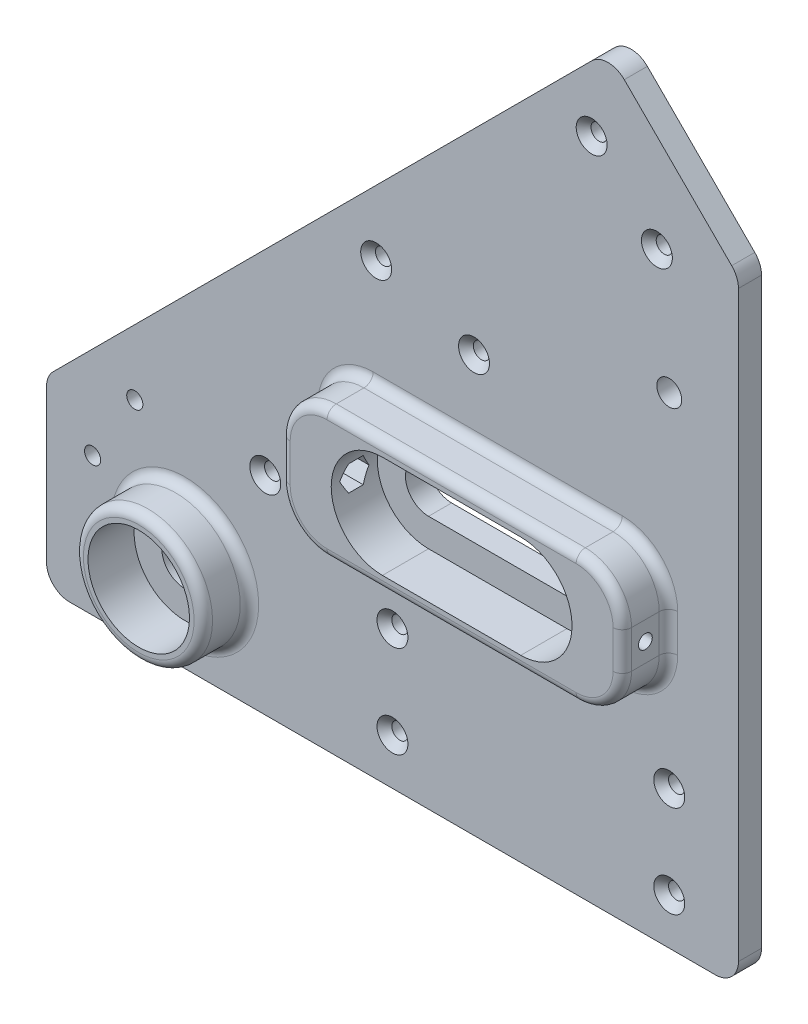
SolidWorks part; units mm, degrees
ref_plane "Front Plane" through (0, 0, 0) normal (0, 0, 1) x (1, 0, 0)
ref_plane "Top Plane" through (0, 0, 0) normal (0, 1, 0) x (1, 0, 0)
ref_plane "Right Plane" through (0, 0, 0) normal (1, 0, 0) x (0, 0, -1)
sketch "Sketch1" plane through (0, 0, 0) normal (0, 0, 1) x (1, 0, 0)
  line L0 (-75, 20) -> (46.7157, 141.7157)
  line L1 (-18.4315, 20) -> (75, 20) construction
  line L2 (-75, 20) -> (-75, -20)
  line L3 (-75, -20) -> (75, -20)
  line L4 (75, 20) -> (75, -20)
  line L5 (-75, 20) -> (75, -20) construction
  line L6 (-75, -20) -> (75, 20) construction
  line L7 (-75, -20) -> (75, -20)
  line L11 (46.7157, 141.7157) -> (75, 113.4315)
  line L12 (75, 113.4315) -> (-18.4315, 20) construction
  line L13 (-75, 0) -> (75, 0) construction
  line L14 (-75, 10) -> (75, 10) construction
  line L15 (-75, -10) -> (75, -10) construction
  line L16 (60.8579, 127.5736) -> (-46.7157, 20) construction
  line L17 (-75, 20) -> (-18.4315, 20) construction
  line L18 (53.7868, 134.6447) -> (-60.8579, 20) construction
  line L19 (67.9289, 120.5025) -> (-32.5736, 20) construction
  line L20 (75, 113.4315) -> (75, 20)
  line L21 (43.1802, 124.0381) -> (57.3223, 109.8959) construction
  line L22 (60, -10) -> (60, 10) construction
  line L23 (-65, -10) -> (-65, 10) construction
  line L24 (7.8202, 40) -> (37.8202, 40) construction
  line L25 (7.8202, 45) -> (37.8202, 45)
  line L26 (7.8202, 35) -> (37.8202, 35)
  line L27 (60, 10) -> (60, 98.4315) construction
  circle A0 centre (-45, 0) radius 5
  circle A1 centre (22.8202, 40) radius 5 construction
  circle A2 centre (-65, -10) radius 1.75
  circle A3 centre (0, 10) radius 1.75
  circle A4 centre (60, -10) radius 1.75
  circle A5 centre (-55.8579, 25) radius 1.75
  circle A6 centre (43.1802, 124.0381) radius 1.75
  circle A8 centre (-27.5736, 25) radius 1.75
  circle A9 centre (57.3223, 109.8959) radius 1.75
  circle A10 centre (22.8202, 40) radius 4 construction
  circle A11 centre (-3.5355, 77.3223) radius 1.75
  circle A12 centre (17.6777, 70.2513) radius 1.75
  circle A13 centre (60, 10) radius 1.75
  circle A14 centre (-65, 10) radius 1.75
  circle A15 centre (0, -10) radius 1.75
  arc A16 (7.8202, 45) -> (7.8202, 35) centre (7.8202, 40) ccw
  arc A17 (37.8202, 35) -> (37.8202, 45) centre (37.8202, 40) ccw
  circle A18 centre (60, 84.2893) radius 2.7
  point P0 (0, 0)
  point P50 (22.8202, 40)
  dimension "D8" = 10
  dimension "D11" = 10
  dimension "D12" = 3.5
  dimension "D17" = 30
  dimension "D18" = 5.4
  dimension "D1" = 40
  dimension "D2" = 40
  dimension "D3" = 45
  dimension "D4" = 10
  dimension "D5" = 10
  dimension "D6" = 10
  dimension "D7" = 10
  dimension "D9" = 30
  dimension "D10" = 150
  dimension "D13" = 10
  dimension "D14" = 15
  dimension "D15" = 5
  dimension "D16" = 15
  dimension "D19" = 10
extrude "Boss-Extrude1" add sketch "Sketch1" along normal blind 5 contours L20 L11 L0 L2 L3 L4 A0 region at (-12.5825, 79.2982, 0)
sketch "Sketch2" plane through (0, 0, 5) normal (0, 0, 1) x (1, 0, 0)
  line L3 (7.8202, 40) -> (37.8202, 40) construction
  line L4 (7.8202, 51.1) -> (37.8202, 51.1)
  line L5 (7.8202, 28.9) -> (37.8202, 28.9)
  line L6 (-14.1798, 54.1) -> (59.8202, 54.1)
  line L7 (-14.1798, 54.1) -> (-14.1798, 25.9)
  line L8 (-14.1798, 25.9) -> (59.8202, 25.9)
  line L9 (59.8202, 54.1) -> (59.8202, 25.9)
  line L10 (-14.1798, 54.1) -> (59.8202, 25.9) construction
  line L11 (-14.1798, 25.9) -> (59.8202, 54.1) construction
  circle A0 centre (-45, 0) radius 11
  circle A1 centre (-45, 0) radius 14
  circle A2 centre (22.8202, 40) radius 11.1 construction
  circle A3 centre (22.8202, 40) radius 14 construction
  arc A6 (7.8202, 51.1) -> (7.8202, 28.9) centre (7.8202, 40) ccw
  arc A7 (37.8202, 28.9) -> (37.8202, 51.1) centre (37.8202, 40) ccw
  point P19 (22.8202, 40)
  dimension "D1" = 22
  dimension "D2" = 28
  dimension "D3" = 22.2
  dimension "D4" = 28
  dimension "D5" = 3
  dimension "D6" = 22
extrude "Boss-Extrude2" add sketch "Sketch2" along normal blind 10
chamfer "Chamfer1" distance 1.6 angle 45 9 edges at (-25.8236, 25, 5) (61.75, -10, 5) (61.75, 10, 5) (1.75, -10, 5) (1.75, 10, 5) (19.4277, 70.2513, 5) (-1.7855, 77.3223, 5) (59.0723, 109.8959, 5) (44.9302, 124.0381, 5)
fillet "Fillet1" radius 10 4 edges at (59.8202, 25.9, 10) (59.8202, 54.1, 10) (-14.1798, 25.9, 10) (-14.1798, 54.1, 10)
sketch "Sketch3" plane through (-14.1798, 0, 0) normal (-1, 0, 0) x (0, 0, 1)
  line L0 (10, 44.1) -> (10, 35.9) construction
  line L1 (15, 44.1) -> (5, 44.1) construction
  line L2 (5, 35.9) -> (15, 35.9) construction
  circle A0 centre (10, 40) radius 1.5
  dimension "D1" = 3
extrude "Cut-Extrude1" cut sketch "Sketch3" against normal through all
ref_plane "Plane1" through (-3.2798, 0, 0) normal (1, 0, 0) x (0, 0, -1)
sketch "Sketch4" plane through (-3.2798, 0, 0) normal (1, 0, 0) x (0, 0, -1)
  line L1 (-6.8246, 40) -> (-8.4123, 42.75)
  line L2 (-8.4123, 42.75) -> (-11.5877, 42.75)
  line L3 (-11.5877, 42.75) -> (-13.1754, 40)
  line L4 (-13.1754, 40) -> (-11.5877, 37.25)
  line L5 (-11.5877, 37.25) -> (-8.4123, 37.25)
  line L6 (-8.4123, 37.25) -> (-6.8246, 40)
  circle A0 centre (-10, 40) radius 2.75 construction
  dimension "D1" = 5.5
extrude "Cut-Extrude3" cut sketch "Sketch4" against normal blind 5 and the other way offset from surface 6 other way up to face at (59.8202, 40, 11.5)
fillet "Fillet2" radius 2 9 edges at (56.8913, 51.1711, 5) (59.8202, 40, 5) (56.8913, 28.8289, 5) (22.8202, 25.9, 5) (-11.2508, 28.8289, 5) (-14.1798, 40, 5) (-11.2508, 51.1711, 5) (-31, 0, 5) (22.8202, 54.1, 5)
fillet "Fillet3" radius 2 9 edges at (56.8913, 51.1711, 15) (59.8202, 40, 15) (56.8913, 28.8289, 15) (22.8202, 25.9, 15) (-11.2508, 28.8289, 15) (-14.1798, 40, 15) (-11.2508, 51.1711, 15) (-31, 0, 15) (22.8202, 54.1, 15)
fillet "Fillet4" radius 5 5 edges at (75, 113.4315, 2.5) (46.7157, 141.7157, 2.5) (75, -20, 2.5) (-75, -20, 2.5) (-75, 20, 2.5)
